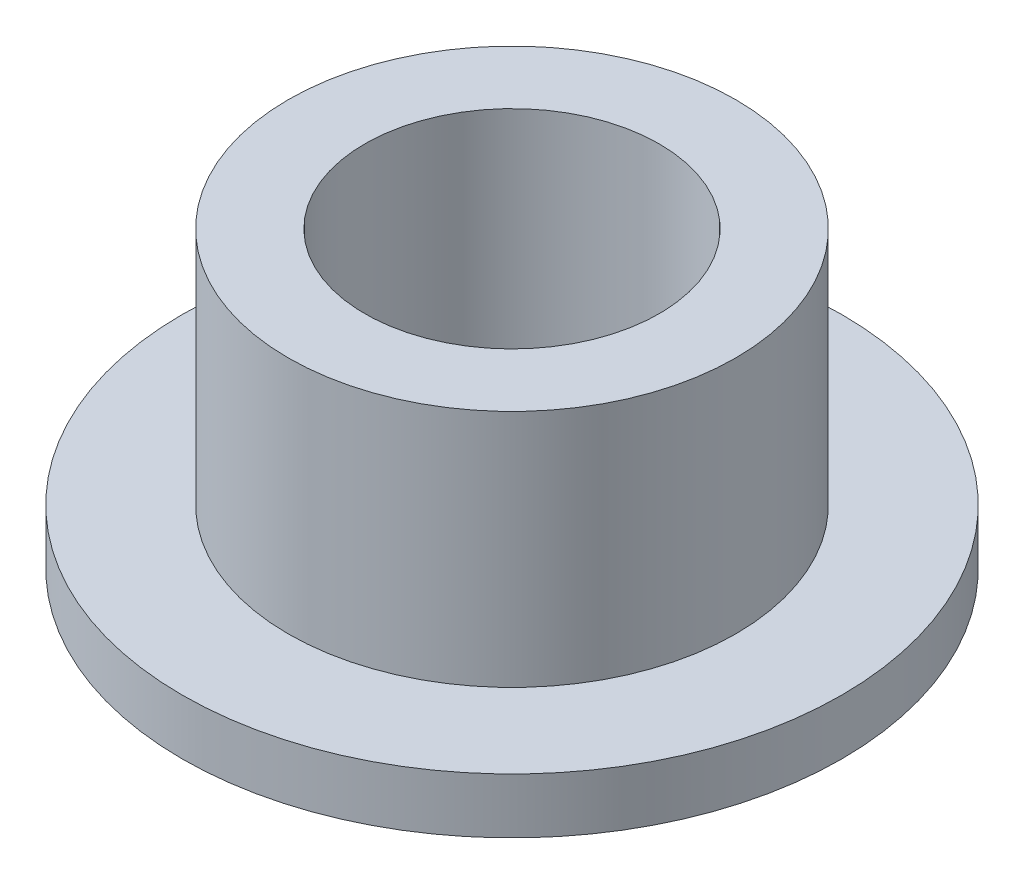
SolidWorks part; units mm, degrees
material "Brass"
ref_plane "Front Plane" through (0, 0, 0) normal (0, 0, 1) x (1, 0, 0)
ref_plane "Top Plane" through (0, 0, 0) normal (0, 1, 0) x (1, 0, 0)
ref_plane "Right Plane" through (0, 0, 0) normal (1, 0, 0) x (0, 0, -1)
sketch "Sketch1" plane through (0, 0, 0) normal (0, 1, 0) x (1, 0, 0)
  circle A0 centre (0, 0) radius 7.112
  dimension "D1" = 14.224
extrude "Boss-Extrude1" add sketch "Sketch1" along normal blind 1.1938
sketch "Sketch3" plane through (0, 0, 0) normal (0, 1, 0) x (1, 0, 0)
  circle A0 centre (0, 0) radius 4.826
  dimension "D1" = 9.652
extrude "Boss-Extrude2" add sketch "Sketch3" along normal blind 6.35
sketch "Sketch4" plane through (0, 0, 0) normal (0, -1, 0) x (1, 0, 0)
  circle A0 centre (0, 0) radius 3.175
  dimension "D1" = 6.35
extrude "Cut-Extrude1" cut sketch "Sketch4" against normal through all
ref_axis "Axis1" [suppressed] through (0, 15.875, 0) along (0, -1, 0)
